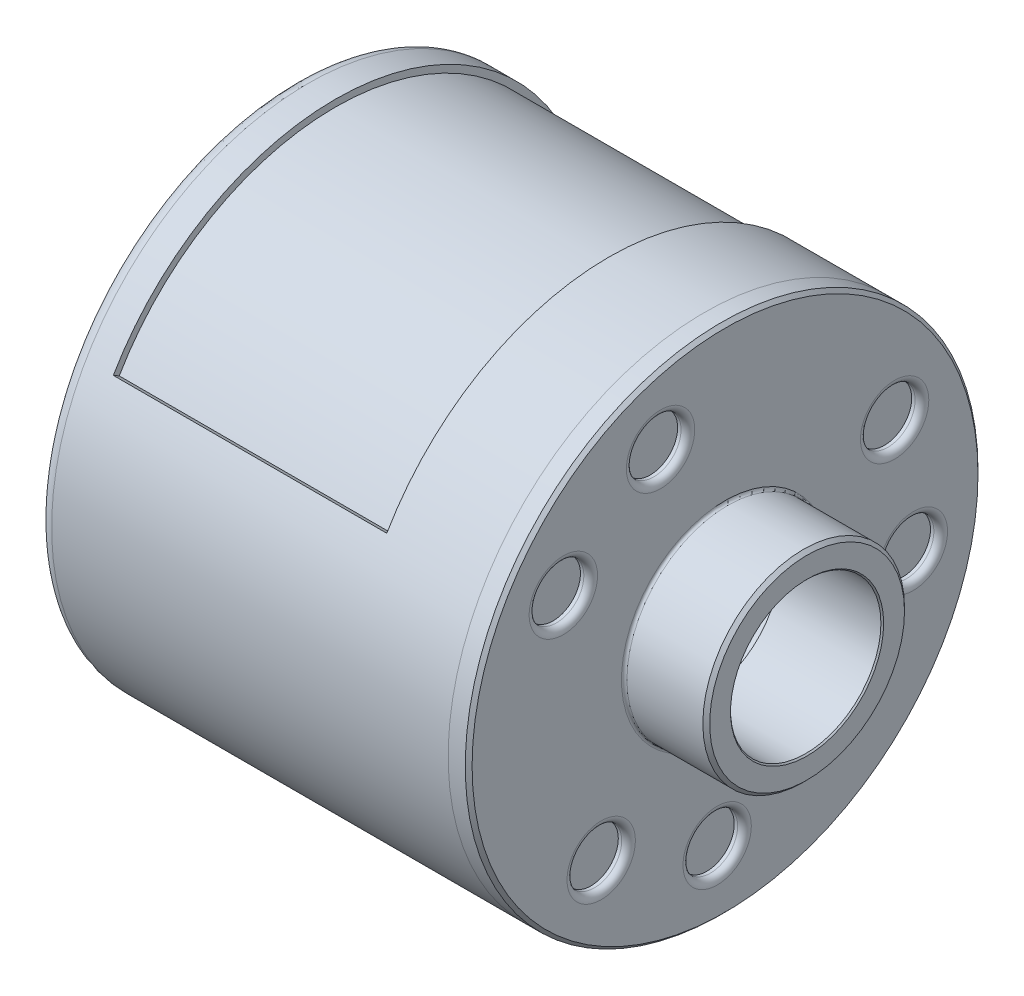
SolidWorks part; units mm, degrees
material "6061 Alloy"
ref_plane "Ön Düzlem" through (0, 0, 0) normal (0, 0, 1) x (1, 0, 0)
ref_plane "Üst Düzlem" through (0, 0, 0) normal (0, 1, 0) x (1, 0, 0)
ref_plane "Sağ Düzlem" through (0, 0, 0) normal (1, 0, 0) x (0, 0, -1)
sketch "Sketch1" plane through (0, 0, 0) normal (1, 0, 0) x (0, 0, -1)
  circle A0 centre (0, 0) radius 25
  dimension "D1" = 50
extrude "Boss-Extrude1" add sketch "Sketch1" along normal blind 40
shell "Shell1" thickness 2 removed face at (40, 0, -25)
scale "Scale9" bodies to scale 101 scale about origin uniform scaling yes scale factor 1.5
sketch "Sketch2" plane through (60, 0, 0) normal (1, 0, 0) x (0, 0, -1)
  circle A0 centre (0, 0) radius 37.5 construction
  circle A1 centre (0, 0) radius 37.5
  circle A2 centre (0, 0) radius 14.75
  circle A3 centre (0, 0) radius 11
  dimension "D1" = 29.5
  dimension "D2" = 22
extrude "Boss-Extrude2" add sketch "Sketch2" along normal blind 3 separate body contours A1
extrude "Boss-Extrude3" add sketch "Sketch2<3>" along normal blind 12 from offset 3 contours A2 A3 region at (60, 0, 14.3328)
sketch "Sketch2<3>" plane through (60, 0, 0) normal (1, 0, 0) x (0, 0, -1) same geometry as "Sketch2"
fillet "Fillet1" radius 0.4 1 edges at (63, 0, -14.75)
chamfer "Chamfer1" distance 0.5 angle 45 1 edges at (63, 0, -37.5)
chamfer "Chamfer2" distance 0.5 angle 45 1 edges at (75, 0, -14.75)
chamfer "Chamfer3" distance 0.2 angle 45 1 edges at (75, 0, -11)
fillet "Fillet2" radius 2 1 edges at (0, 0, -37.5)
sketch "Sketch8" plane through (63, 0, 0) normal (1, 0, 0) x (0, 0, -1)
  circle A1 centre (0, 0) radius 11
  circle A2 centre (0, 0) radius 11
  dimension "D1" = 0
extrude "Cut-Extrude2" cut sketch "Sketch8" against normal blind 10
sketch "Sketch9" plane through (63, 0, 0) normal (1, 0, 0) x (0, 0, -1)
  circle A0 centre (0, 0) radius 28 construction
  circle A2 centre (27.5479, -5.0111) radius 4
  circle A4 centre (-18.1137, -21.3516) radius 4
  circle A5 centre (-9.4342, 26.3628) radius 4
  circle A6 centre (24.805, 12.9889) radius 4
  circle A7 centre (-1.1538, -27.9762) radius 4
  circle A8 centre (-23.6512, 14.9873) radius 4
  dimension "D1" = 56
  dimension "D2" = 8
  dimension "D3" = 3
  dimension "D4" = 8
  dimension "D5" = 18
  dimension "D6" = 3
extrude "Cut-Extrude3" cut sketch "Sketch9" against normal blind 1.5
fillet "Fillet3" radius 1 1 edges at (63, -5.0111, -31.5479)
fillet "Fillet4" radius 1 2 edges at (63, -21.3516, 14.1137) (63, 26.3628, 5.4342)
fillet "Fillet5" radius 1 3 edges at (63, 14.9873, 19.6512) (63, -27.9762, -2.8462) (63, 12.9889, -28.805)
ref_plane "Plane2" through (46, 0, 0) normal (1, 0, 0) x (0, 0, -1)
sketch "Sketch11" plane through (46, 0, 0) normal (1, 0, 0) x (0, 0, -1)
  line L0 (31.6099, 18.25) -> (32.476, 18.75)
  line L1 (0, 0) -> (0, 43.333) construction
  line L2 (-31.6099, 18.25) -> (-32.476, 18.75)
  arc A0 (32.476, 18.75) -> (-32.476, 18.75) centre (0, 0) ccw
  circle A1 centre (0, 0) radius 37.5 construction
  arc A2 (31.6099, 18.25) -> (-31.6099, 18.25) centre (0, 0) ccw
  dimension "D1" = 60
  dimension "D2" = 1
extrude "Cut-Extrude4" cut sketch "Sketch11" against normal blind 40
